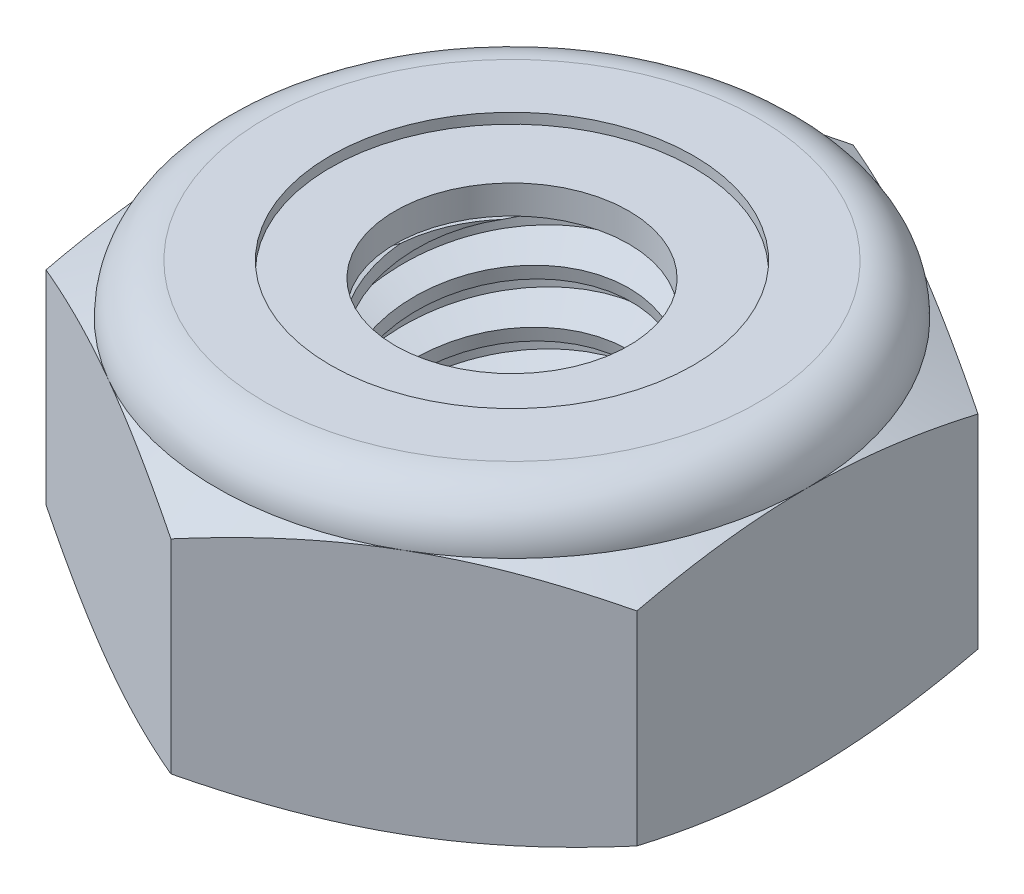
SolidWorks part; units mm, degrees
ref_plane "Front" through (0, 0, 0) normal (0, 0, 1) x (1, 0, 0)
ref_plane "Top" through (0, 0, 0) normal (0, 1, 0) x (1, 0, 0)
ref_plane "Right" through (0, 0, 0) normal (1, 0, 0) x (0, 0, -1)
sketch "Sketch1" plane through (0, 0, 0) normal (0, 1, 0) x (1, 0, 0)
  line L1 (0, 5.041) -> (-4.3656, 2.5205)
  line L2 (-4.3656, 2.5205) -> (-4.3656, -2.5205)
  line L3 (-4.3656, -2.5205) -> (0, -5.041)
  line L4 (0, -5.041) -> (4.3656, -2.5205)
  line L5 (4.3656, -2.5205) -> (4.3656, 2.5205)
  line L6 (4.3656, 2.5205) -> (0, 5.041)
  circle A0 centre (0, 0) radius 4.3656 construction
  dimension "Hex Flats" = 8.7312
extrude "Extrude1" add sketch "Sketch1" along normal blind 4.3656
sketch "Sketch2" plane through (0, 0, 0) normal (1, 0, 0) x (0, 0, -1)
  line L0 (-2.0828, 0) -> (-2.0828, 4.3656) construction
  line L1 (0, 0) -> (2.0828, 0)
  line L2 (0, 0) -> (0, 4.3656)
  line L3 (0, 4.3656) -> (2.0828, 4.3656)
  line L4 (2.0828, 0) -> (2.0828, 4.3656)
  line L5 (-2.5205, 4.3656) -> (2.5205, 4.3656) construction
  line L7 (0, -2.0828) -> (0, 0) construction
  dimension "Thread Dia" = 4.1656
revolve "Revolve1" add sketch "Sketch2" angle 360 about L7
sketch "Sketch3" plane through (0, 0, 0) normal (1, 0, 0) x (0, 0, -1)
  line L0 (2.0828, 4.3656) -> (-2.0828, 4.3656) construction
  line L1 (-2.0828, 4.3656) -> (-2.0828, 3.5719) construction
  line L2 (-2.0828, 3.5719) -> (2.0828, 4.3656) construction
  line L3 (2.0828, 4.3656) -> (2.1014, 4.2682) construction
  line L4 (2.1014, 4.2682) -> (2.2314, 3.5859)
  line L5 (2.2314, 3.5859) -> (1.7629, 3.7491)
  line L6 (1.7629, 3.7491) -> (1.7258, 3.9441)
  line L7 (1.7258, 3.9441) -> (2.1014, 4.2682)
  line L8 (1.7443, 3.8466) -> (2.1664, 3.927) construction
  line L9 (2.0828, 4.3656) -> (2.0828, 3.9111) construction
  line L10 (2.0828, 3.9111) -> (-2.0828, 3.1174) construction
  line L11 (-2.0828, 3.1174) -> (-2.0828, 3.5719) construction
  line L12 (-0.1622, 4.3656) -> (0.1622, 2.6628) construction
  line L13 (-2.0828, 0) -> (-2.0828, 4.3656) construction
  line L14 (0, 4.3656) -> (2.0828, 4.3656) construction
  line L15 (2.0828, 0) -> (2.0828, 4.3656) construction
  point P13 (0, 3.5142)
  dimension "D1" = 0.0992
  dimension "D2" = 0.1984
  dimension "Thread Pitch" = 0.7937
  dimension "D4" = 60
  dimension "D5" = 0.7937
revolve "Cut-Revolve1" cut sketch "Sketch3" angle 360 about L12
pattern_linear "LPattern1" count 6 spacing 0.7937 along (0, -1, 0) count 2 spacing 0.7937 along (0, 1, 0) of "Cut-Revolve1"
sketch "Sketch4" plane through (0, 0, 0) normal (1, 0, 0) x (0, 0, -1)
  line L0 (0, 4.3656) -> (2.0828, 4.3656)
  line L1 (2.0828, 4.3656) -> (1.7258, 4.1991)
  line L2 (1.7258, 4.1991) -> (1.7258, 0.1665)
  line L3 (1.7258, 0.1665) -> (2.0828, 0)
  line L4 (2.0828, 0) -> (0, 0)
  line L5 (0, 0) -> (0, 4.3656)
  line L6 (2.0828, 0) -> (2.0828, 4.3656) construction
  line L7 (0, 4.3656) -> (2.0828, 4.3656) construction
  line L8 (0, 0) -> (2.0828, 0) construction
  line L9 (0, 0) -> (0, 4.3656) construction
  line L10 (0, 4.3656) -> (0, 4.7596) construction
  dimension "D1" = 25
revolve "Cut-Revolve2" cut sketch "Sketch4" angle 360 about L10
combine bodies "Combine1" operation type subtract main body 112 bodies to subtract 111
sketch "Sketch5" plane through (0, 0, 0) normal (1, 0, 0) x (0, 0, -1)
  line L0 (0, 0) -> (4.3656, 0)
  line L1 (4.3656, 0) -> (5.041, 0.3149)
  line L2 (5.041, 0.3149) -> (5.041, 3.3231)
  line L3 (5.041, 3.3231) -> (4.3656, 3.638)
  line L4 (3.638, 4.3656) -> (3.638, 5.6356)
  line L5 (3.638, 5.6356) -> (6.311, 5.6356)
  line L6 (6.311, 5.6356) -> (6.311, -1.27)
  line L7 (6.311, -1.27) -> (0, -1.27)
  line L8 (0, -1.27) -> (0, 0)
  line L9 (4.3656, 3.638) -> (4.3656, 0) construction
  line L10 (0, 0) -> (2.0828, 0) construction
  line L13 (5.041, 1.819) -> (6.311, 1.819) construction
  line L14 (5.041, 4.3656) -> (5.041, 0) construction
  line L15 (0, 0) -> (0, 5.6356) construction
  line L20 (0, 5.6356) -> (3.638, 5.6356) construction
  line L22 (0, 4.3656) -> (2.0828, 4.3656) construction
  arc A0 (4.3656, 3.638) -> (3.638, 4.3656) centre (3.638, 3.638) ccw
  dimension "D1" = 25
  dimension "D2" = 1.27
  dimension "D3" = 4.3656
  dimension "D4" = 0.7276
revolve "Cut-Revolve3" cut sketch "Sketch5" angle 360 about L15
sketch "Sketch6" plane through (0, 0, 0) normal (1, 0, 0) x (0, 0, -1)
  line L0 (0, 3.638) -> (4.2132, 3.638)
  line L1 (3.638, 4.2132) -> (2.6819, 4.2132)
  line L2 (0, 5.6356) -> (0, 3.638)
  line L3 (2.6819, 5.6356) -> (0, 5.6356)
  line L4 (0, 5.6356) -> (3.638, 5.6356) construction
  line L5 (0, 0) -> (0, 5.6356) construction
  line L6 (0, 5.6356) -> (0, 44.323) construction
  line L7 (2.6819, 4.2132) -> (2.6819, 5.6356)
  line L8 (3.638, 4.3656) -> (3.638, 4.2132) construction
  line L9 (2.6819, 4.2132) -> (1.7258, 4.2132) construction
  line L10 (1.7258, 4.2132) -> (1.7258, 4.1991) construction
  arc A0 (4.2132, 3.638) -> (3.638, 4.2132) centre (3.638, 3.638) ccw
  arc A1 (4.3656, 3.638) -> (3.638, 4.3656) centre (3.638, 3.638) ccw construction
  dimension "D1" = 0.1524
revolve "Cut-Revolve4" cut sketch "Sketch6" angle 360 about L6
sketch "Sketch7" plane through (0, 0, 0) normal (1, 0, 0) x (0, 0, -1)
  line L0 (1.7258, 3.7142) -> (4.1312, 3.7142)
  line L1 (3.638, 4.137) -> (1.7258, 4.137)
  line L2 (1.7258, 4.137) -> (1.7258, 3.7142)
  line L3 (1.7258, 3.7142) -> (0, 3.7142) construction
  line L4 (0, 3.7142) -> (0, 4.137) construction
  line L5 (0, 4.137) -> (1.7258, 4.137) construction
  line L6 (1.7258, 3.7142) -> (1.7258, 3.638) construction
  line L7 (0, 3.638) -> (4.2132, 3.638) construction
  line L8 (3.638, 4.137) -> (3.638, 4.2132) construction
  arc A0 (4.1312, 3.7142) -> (3.638, 4.137) centre (3.638, 3.638) ccw
  arc A2 (4.2132, 3.638) -> (3.638, 4.2132) centre (3.638, 3.638) ccw construction
  dimension "D1" = 0.0762
revolve "Revolve2" add sketch "Sketch7" angle 360 about L4
equation "\"D1@Sketch3\"=\"Thread Pitch@Sketch3\"/8"
equation "\"D2@Sketch3\"=\"Thread Pitch@Sketch3\"/4"
equation "\"D5@Sketch3\"=\"Thread Pitch@Sketch3\""
equation "\"D4@LPattern1\"=\"Thread Pitch@Sketch3\""
equation "\"D3@LPattern1\"=\"Thread Pitch@Sketch3\""
equation "\"D1@LPattern1\"=\"Height@Extrude1\"/\"Thread Pitch@Sketch3\""
equation "\"D4@Sketch5\"=\"Height@Extrude1\"/6"
